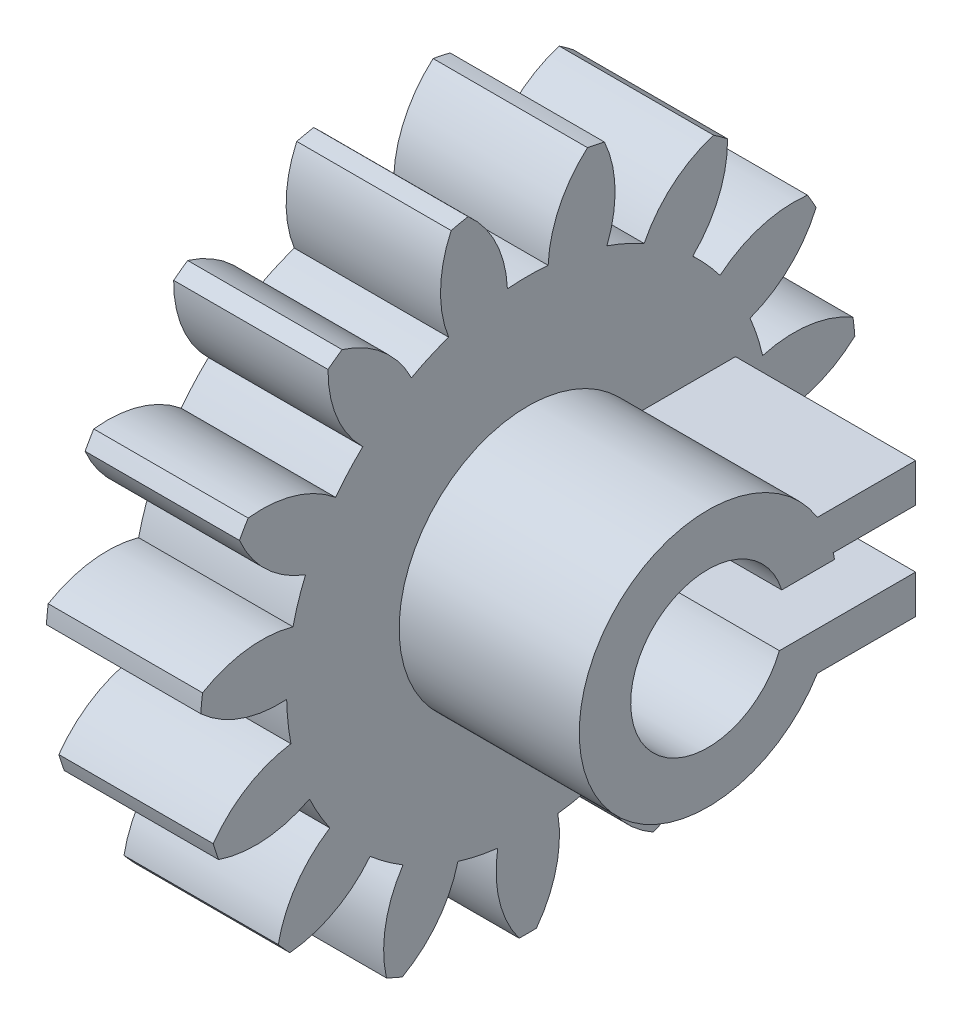
SolidWorks part; units mm, degrees
ref_plane "Plane1" through (0, 0, 0) normal (0, 0, 1) x (1, 0, 0)
ref_plane "Plane2" through (0, 0, 0) normal (0, 1, 0) x (1, 0, 0)
ref_plane "Plane3" through (0, 0, 0) normal (1, 0, 0) x (0, 0, -1)
sketch "HoldingSke" plane through (0, 0, 0) normal (0, 1, 0) x (1, 0, 0)
  line L0 (0, 0) -> (0.644, -0.1725)
  line L1 (-15, 0) -> (100, 0) construction
  line L2 (0, 0) -> (-2.1039, 2.3779)
  line L3 (0, 0) -> (-11.863, 4.5341)
  line L4 (0, 0) -> (8.3417, 2.2352)
  line L5 (0, 0) -> (-46.8476, -17.4728)
  line L6 (0, 0) -> (-4.9738, -3.3558)
  line L7 (-2.1039, 2.3779) -> (8.6586, 51.2059)
  line L8 (-76.2, 54.61) -> (-75.2, 54.61)
  line L9 (-71.009, 38.7566) -> (-53.1078, 45.2721)
  line L10 (-76.2, 71.12) -> (104.1128, 71.12)
  line L11 (0, 0) -> (-6, 0)
  line L12 (-76.2, 101.6) -> (-76.147, 101.6)
  line L13 (24.9733, 27.94) -> (52.9518, 28.4284)
  line L14 (24.9733, 27.94) -> (24.9743, 27.94)
  line L15 (24.9733, 27.94) -> (100.4006, 29.5858)
  line L16 (-63.627, -1.5) -> (-12.827, -1.5)
  circle A0 centre (0, 0) radius 3
  circle A1 centre (0, 0) radius 9.374
  circle A2 centre (0, 0) radius 37.5
  circle A3 centre (0, 0) radius 3
  dimension "Num_teeth" = 15
  dimension "Pitch_radius" = 180.3128
  dimension "Width" = 6
  dimension "Thickness" = 6
sketch "BasProSke" plane through (0, 0, 0) normal (0, 1, 0) x (1, 0, 0)
  line L0 (-10, 0) -> (60, 0) construction
  line L1 (0, 0) -> (0, 12.75)
  line L2 (0, 0) -> (6, 0)
  line L3 (6, 0) -> (6, 12.75)
  line L4 (6, 12.75) -> (0, 12.75)
  dimension "Thickness" = 6
  dimension "Diameter" = 25.5
revolve "Base-Revolve" add sketch "BasProSke" angle 360 about L0
sketch "TooCutSke" plane through (0, 0, 0) normal (1, 0, 0) x (0, 0, -1)
  line L1 (0, 0) -> (0, 107) construction
  line L2 (0, 0) -> (-1.2686, 11.1782) construction
  line L3 (0, 0) -> (-4.6563, 21.9061) construction
  line L4 (-1.2686, 11.1782) -> (-2.3281, 10.953) construction
  arc A0 (0.7915, 9.3405) -> (-0.7915, 9.3405) centre (0, 0) ccw
  arc A1 (2.3447, 12.5584) -> (-2.3447, 12.5584) centre (0, 0) ccw
  circle A2 centre (0, 0) radius 11.25 construction
  circle A3 centre (0, 0) radius 10.5715 construction
  arc A4 (-0.7915, 9.3405) -> (-2.3447, 12.5584) centre (-5.2877, 9.1541) ccw
  arc A5 (2.3447, 12.5584) -> (0.7915, 9.3405) centre (5.2877, 9.1541) ccw
extrude "ToothCut" cut sketch "TooCutSke" along normal through all
fillet "Breaks" [suppressed] radius 0.03 tangent propagation no
fillet "RootFillets" [suppressed] radius 0.376
pattern_circular "TeethCuts" count 15 every 24 about axis through (-10, 0, 0) along (1, 0, 0) of "ToothCut", "RootFillets", "Breaks"
sketch "HubNeaOneSke" plane through (0, 0, 0) normal (-1, 0, 0) x (0, 0, 1)
  circle A0 centre (0, 0) radius 9.374
  dimension "Diameter" = 18.748
extrude "HubNearOne" [suppressed] add sketch "HubNeaOneSke" along normal blind 44.0001
sketch "HubNeaBotSke" plane through (0, 0, 0) normal (-1, 0, 0) x (0, 0, 1)
  circle A0 centre (0, 0) radius 9.374
  dimension "Diameter" = 18.748
extrude "HubNearBoth" [suppressed] add sketch "HubNeaBotSke" along normal blind 22
ref_plane "FarPln" through (6, 0, 0) normal (1, 0, 0) x (0, 0, -1)
sketch "HubFarSke" plane through (6, 0, 0) normal (1, 0, 0) x (0, 0, -1)
  circle A0 centre (0, 0) radius 9.374
  dimension "Diameter" = 18.748
extrude "HubFar" [suppressed] add sketch "HubFarSke" along normal blind 22
sketch "BorSke" plane through (0, 0, 0) normal (1, 0, 0) x (0, 0, -1)
  circle A0 centre (0, 0) radius 3
  dimension "Diameter" = 6
extrude "Bore" cut sketch "BorSke" along normal mid plane 100.0001
sketch "KeySke" plane through (0, 0, 0) normal (1, 0, 0) x (0, 0, -1)
  line L0 (-1, 0) -> (-1, 4)
  line L1 (-1, 4) -> (1, 4)
  line L2 (1, 4) -> (1, 0)
  line L3 (0, 0) -> (0, 34) construction
  line L4 (-1, 0) -> (1, 0)
  dimension "Width" = 2
extrude "Keyway" [suppressed] cut sketch "KeySke" along normal mid plane 100.0001
pattern_circular "Keyway2" [suppressed] count 2 every 90 about axis through (-10, 0, 0) along (1, 0, 0) reverse direction yes
sketch "Sketch1" plane through (6, 0, 0) normal (1, 0, 0) x (0, 0, -1)
  circle A0 centre (0, 0) radius 5
  circle A1 centre (0, 0) radius 3 construction
  circle A2 centre (0, 0) radius 3
  dimension "D1" = 2
extrude "Boss-Extrude1" add sketch "Sketch1" along normal blind 7
sketch "Sketch2" plane through (13, 0, 0) normal (1, 0, 0) x (0, 0, -1)
  line L1 (1.5395, -1.1254) -> (6.0126, -1.1254)
  line L2 (1.5395, -1.1254) -> (1.5395, 0.8746)
  line L3 (1.5395, 0.8746) -> (6.0126, 0.8746)
  line L4 (6.0126, -1.1254) -> (6.0126, 0.8746)
  line L5 (1.5395, -1.1254) -> (6.0126, 0.8746) construction
  line L6 (1.5395, 0.8746) -> (6.0126, -1.1254) construction
  point P0 (3.776, -0.1254)
  dimension "D1" = 2
extrude "Cut-Extrude1" cut sketch "Sketch2" against normal up to surface (7 mm away) contours L3 L4 L1 L2 up to face at (6, 0, 0)
sketch "Sketch3" plane through (0, -1.1254, 0) normal (0, 1, 0) x (1, 0, 0)
  line L1 (6, 2.7809) -> (13, 2.7809)
  line L2 (6, 2.7809) -> (6, 8.0738)
  line L3 (6, 8.0738) -> (13, 8.0738)
  line L4 (13, 2.7809) -> (13, 8.0738)
extrude "Boss-Extrude2" add sketch "Sketch3" against normal blind 1.5
mirror "Mirror2" about plane through (0, 0, 0) normal (0, 1, 0) of "Boss-Extrude2"
equation "' \"Module@HoldingSke\" = 6.35"
equation "' \"Num_teeth@HoldingSke\" = 12"
equation "' \"Ap@HoldingSke\" =  20"
equation "' \"Ap@HoldingSke\" = 20"
equation "' \"Width@HoldingSke\" = 0.5 * 25.4"
equation "' \"Hub_dia@HoldingSke\"= 1 * 25.4"
equation "' \"Hub_dia@HoldingSke\" = 1 * 25.4"
equation "' \"Overall_len@HoldingSke\" = 1.0 * 25.4"
equation "' \"Bore@HoldingSke\" = 0.75 * 25.4"
equation "' \"T_dim@HoldingSke\" = 0.1 * 25.4"
equation "' \"Width@KeySke\" = 0.25 * 25.4"
equation "' \"Show_teeth@HoldingSke\" = 13"
equation "' \"Backlash@HoldingSke\" = 0.009 * 25.4"
equation "' \"Addendum_fac@HoldingSke\" = 1.0"
equation "' \"Dedendum_fac@HoldingSke\" = 1.25"
equation "' \"Dedendum_add@HoldingSke\" = 0.00005 * 25.4"
equation "' \"Clearance_fac@HoldingSke\" = 0.25"
equation "\"Pitch@HoldingSke\" = 1 / \"Module@HoldingSke\""
equation "\"Overcut_dia@TooCutSke\" = (\"Num_teeth@HoldingSke\" + 2 * \"Addendum_fac@HoldingSke\") / \"Pitch@HoldingSke\" + 0.002 * 25.4"
equation "\"Pitch_dia@TooCutSke\" = \"Num_teeth@HoldingSke\" / \"Pitch@HoldingSke\""
equation "\"Base_dia@TooCutSke\" = \"Num_teeth@HoldingSke\" / \"Pitch@HoldingSke\" * cos((\"Ap@HoldingSke\"  * 3.14159265 / 180))"
equation "\"Root_dia@TooCutSke\" = (\"Num_teeth@HoldingSke\" + 2) / \"Pitch@HoldingSke\" - 2 * (\"Addendum_fac@HoldingSke\" + \"Dedendum_fac@HoldingSke\") / \"Pitch@HoldingSke\" - \"Dedendum_add@HoldingSke\" * 2"
equation "\"Half_ang@TooCutSke\" = 180 / \"Num_teeth@HoldingSke\""
equation "\"Half_CT@TooCutSke\" = \"Num_teeth@HoldingSke\" / \"Pitch@HoldingSke\" * sin((3.14159265 / 2 / \"Num_teeth@HoldingSke\")) / 2 - 7 * \"Backlash@HoldingSke\" / 4"
equation "\"Flank_rad@TooCutSke\" = \"Num_teeth@HoldingSke\" / \"Pitch@HoldingSke\" / 5"
equation "\"Radius@RootFillets\" = \"Clearance_fac@HoldingSke\" / \"Pitch@HoldingSke\" + \"Dedendum_add@HoldingSke\""
equation "\"Break_rad@Breaks\" = 0.02 / \"Pitch@HoldingSke\""
equation "\"Thickness@HoldingSke\" = \"Width@HoldingSke\""
equation "\"OAL@HoldingSke\" = \"Thickness@HoldingSke\""
equation "\"MHD@HoldingSke\" = (\"Num_teeth@HoldingSke\" + 2) / \"Pitch@HoldingSke\" - 2 * (\"Addendum_fac@HoldingSke\" + \"Dedendum_fac@HoldingSke\")  / \"Pitch@HoldingSke\" - \"Dedendum_add@HoldingSke\" * 2"
equation "\"MBD@HoldingSke\" = (\"Num_teeth@HoldingSke\" + 2) / \"Pitch@HoldingSke\" - 2 * (\"Addendum_fac@HoldingSke\" + \"Dedendum_fac@HoldingSke\")  / \"Pitch@HoldingSke\" - \"Dedendum_add@HoldingSke\" * 2 - 0.002 * 25.4"
equation "\"MHD@HoldingSke\" = ((sgn( \"MHD@HoldingSke\" - \"Hub_dia@HoldingSke\" )-1)*( \"MHD@HoldingSke\" - \"Hub_dia@HoldingSke\" ))/-2+ \"Hub_dia@HoldingSke\""
equation "\"MBD@HoldingSke\" = ((sgn( \"MBD@HoldingSke\" - \"Bore@HoldingSke\" )-1)*( \"MBD@HoldingSke\" - \"Bore@HoldingSke\" ))/-2+ \"Bore@HoldingSke\""
equation "\"OAL@HoldingSke\" = ((sgn( \"OAL@HoldingSke\" - \"Overall_len@HoldingSke\" )+1)*( \"OAL@HoldingSke\" - \"Overall_len@HoldingSke\" ))/2 + \"Overall_len@HoldingSke\" + 0.000002 * 25.4"
equation "\"Num_teeth@TeethCuts\" = int( \"Show_teeth@HoldingSke\" ) + 1"
equation "\"Num_teeth@TeethCuts\" = ((sgn( \"Num_teeth@TeethCuts\" - \"Num_teeth@HoldingSke\" )-1)*( \"Num_teeth@TeethCuts\" - \"Num_teeth@HoldingSke\" ))/-2+ \"Num_teeth@HoldingSke\""
equation "\"Num_teeth@TeethCuts\" = ((sgn( \"Num_teeth@TeethCuts\" - 2.0)+1)*( \"Num_teeth@TeethCuts\" - 2.0))/2 +2.0"
equation "\"Angle@TeethCuts\" = 360.0 / \"Num_teeth@HoldingSke\""
equation "\"Diameter@BasProSke\" = (\"Num_teeth@HoldingSke\" + 2 * \"Addendum_fac@HoldingSke\") / \"Pitch@HoldingSke\""
equation "\"Thickness@BasProSke\"  = \"Thickness@HoldingSke\""
equation "' \"Fillet_rad@BasProSke\" =  \"Thickness@HoldingSke\" * 0.05"
equation "' \"Fillet_rad@BasProSke\" = \"Thickness@HoldingSke\" * 0.05"
equation "\"MHD@HoldingSke\" = ((sgn( \"MHD@HoldingSke\" - \"Root_dia@TooCutSke\" )-1)*( \"MHD@HoldingSke\" - \"Root_dia@TooCutSke\" ))/-2+ \"Root_dia@TooCutSke\""
equation "\"Diameter@HubNeaOneSke\" = \"MHD@HoldingSke\""
equation "\"Length@HubNearOne\" = \"OAL@HoldingSke\" - \"Thickness@BasProSke\""
equation "\"Diameter@HubNeaBotSke\" = \"MHD@HoldingSke\""
equation "\"Length@HubNearBoth\" = ( \"OAL@HoldingSke\" - \"Thickness@BasProSke\" ) / 2.0"
equation "\"Thickness@FarPln\" = \"Thickness@BasProSke\""
equation "\"Diameter@HubFarSke\" = \"MHD@HoldingSke\""
equation "\"Length@HubFar\" = ( \"OAL@HoldingSke\" - \"Thickness@BasProSke\" ) / 2.0"
equation "\"Diameter@BorSke\" = \"MBD@HoldingSke\""
equation "\"D1@Bore\" = \"OAL@HoldingSke\" * 2.0"
equation "\"D1@Keyway\" = \"OAL@HoldingSke\" * 2.0"
equation "\"Offset@KeySke\" = \"T_dim@HoldingSke\" + \"MBD@HoldingSke\" / 2.0"
